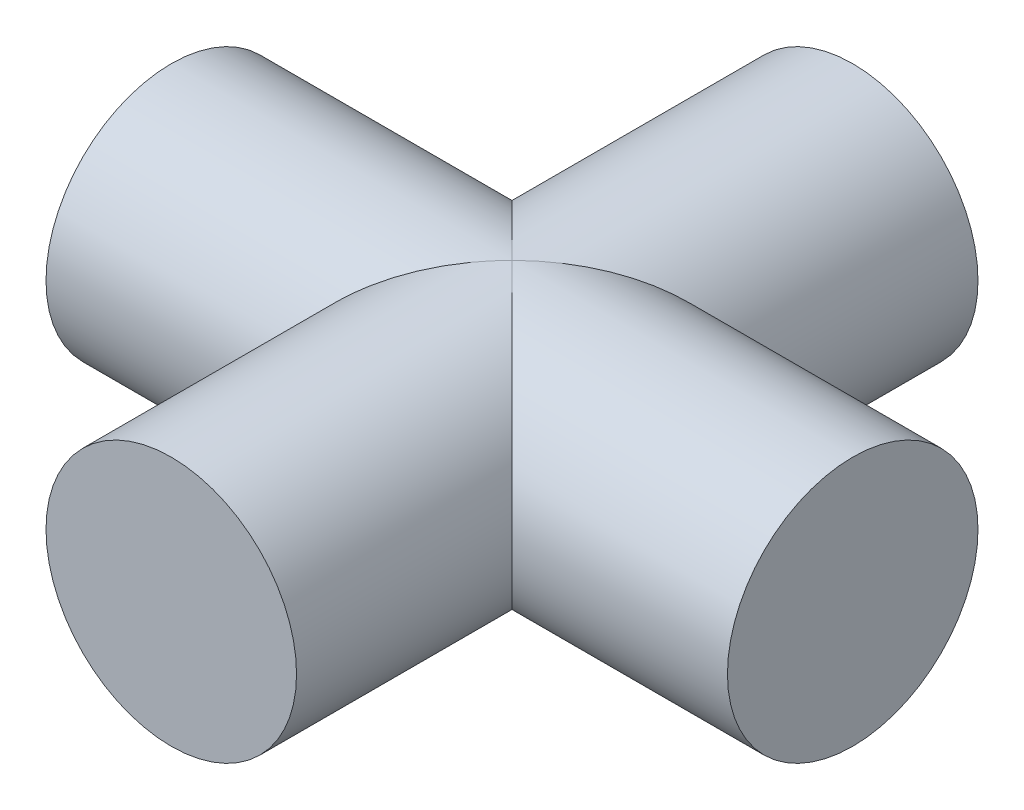
SolidWorks part; units mm, degrees
ref_plane "Front Plane" through (0, 0, 0) normal (0, 0, 1) x (1, 0, 0)
ref_plane "Top Plane" through (0, 0, 0) normal (0, 1, 0) x (1, 0, 0)
ref_plane "Right Plane" through (0, 0, 0) normal (1, 0, 0) x (0, 0, -1)
sketch "Sketch1" plane through (0, 0, 0) normal (0, 0, 1) x (1, 0, 0)
  circle A0 centre (0, 0) radius 12.5
  dimension "D1" = 25
extrude "Boss-Extrude1" add sketch "Sketch1" along normal blind 68
sketch "Sketch2" plane through (0, 0, 0) normal (1, 0, 0) x (0, 0, -1)
  circle A0 centre (-34, 0) radius 12.5
extrude "Boss-Extrude2" add sketch "Sketch2" along normal blind 34 and the other way blind 34
